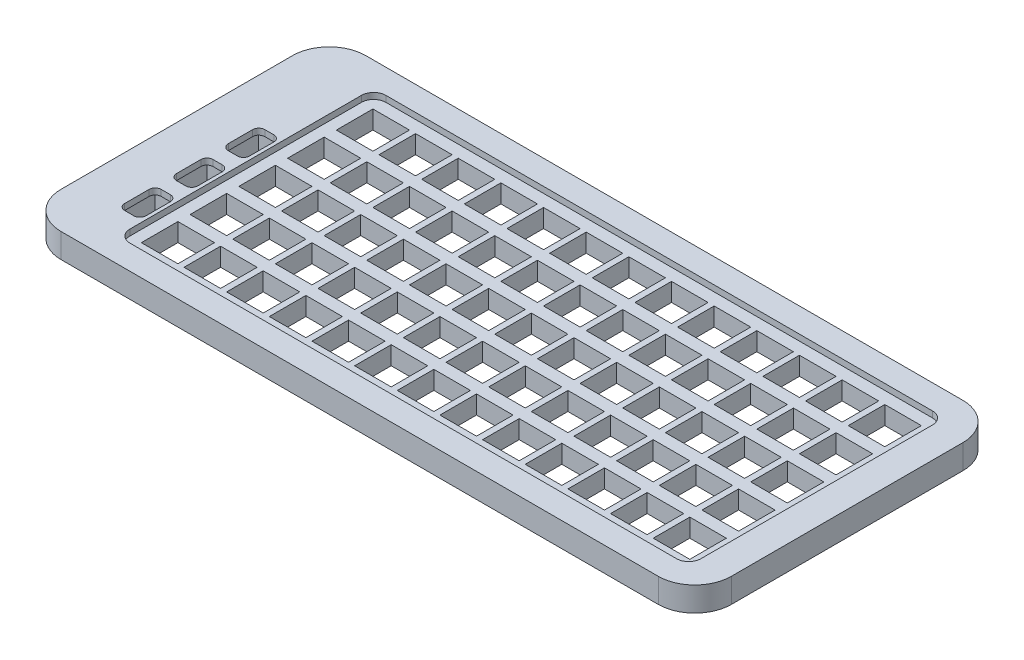
SolidWorks part; units mm, degrees
ref_plane "前视基准面" through (0, 0, 0) normal (0, 0, 1) x (1, 0, 0)
ref_plane "上视基准面" through (0, 0, 0) normal (0, 1, 0) x (1, 0, 0)
ref_plane "右视基准面" through (0, 0, 0) normal (1, 0, 0) x (0, 0, -1)
other "Configuration Table"
sketch "草图1" plane through (0, 0, 0) normal (0, 1, 0) x (1, 0, 0)
  line L1 (-55, -25) -> (55, -25)
  line L2 (-55, -25) -> (-55, 25)
  line L3 (-55, 25) -> (55, 25)
  line L4 (55, -25) -> (55, 25)
  line L5 (-55, -25) -> (55, 25) construction
  line L6 (-55, 25) -> (55, -25) construction
  point P0 (0, 0)
  dimension "D1" = 50
  dimension "D2" = 110
extrude "凸台-拉伸1" add sketch "草图1" along normal blind 3
sketch "草图2" plane through (0, 0, 0) normal (0, -1, 0) x (1, 0, 0)
  line L0 (46.3251, 14.2) -> (44.0251, 17.8) construction
  line L1 (48.1751, 11) -> (48.1751, 5)
  line L2 (48.1751, 19) -> (42.1751, 19)
  line L3 (48.1751, 19) -> (48.1751, 13)
  line L4 (48.1751, 13) -> (42.1751, 13)
  line L5 (42.1751, 19) -> (42.1751, 13)
  line L6 (48.1751, 19) -> (42.1751, 13) construction
  line L7 (48.1751, 13) -> (42.1751, 19) construction
  line L8 (48.1751, 5) -> (42.1751, 5)
  line L9 (42.1751, 11) -> (42.1751, 5)
  line L10 (48.1751, 11) -> (42.1751, 11)
  line L11 (48.1751, 3) -> (48.1751, -3)
  line L12 (48.1751, -3) -> (42.1751, -3)
  line L13 (42.1751, 3) -> (42.1751, -3)
  line L14 (48.1751, 3) -> (42.1751, 3)
  line L15 (48.1751, -5) -> (48.1751, -11)
  line L16 (48.1751, -11) -> (42.1751, -11)
  line L17 (42.1751, -5) -> (42.1751, -11)
  line L18 (48.1751, -5) -> (42.1751, -5)
  line L19 (48.1751, -13) -> (48.1751, -19)
  line L20 (48.1751, -19) -> (42.1751, -19)
  line L21 (42.1751, -13) -> (42.1751, -19)
  line L22 (48.1751, -13) -> (42.1751, -13)
  line L23 (41.1751, 11) -> (41.1751, 5)
  line L24 (41.1751, 5) -> (35.1751, 5)
  line L25 (35.1751, 11) -> (35.1751, 5)
  line L26 (41.1751, 11) -> (35.1751, 11)
  line L27 (41.1751, 3) -> (41.1751, -3)
  line L28 (41.1751, -3) -> (35.1751, -3)
  line L29 (35.1751, 3) -> (35.1751, -3)
  line L30 (41.1751, 3) -> (35.1751, 3)
  line L31 (41.1751, -5) -> (41.1751, -11)
  line L32 (41.1751, -11) -> (35.1751, -11)
  line L33 (35.1751, -5) -> (35.1751, -11)
  line L34 (41.1751, -5) -> (35.1751, -5)
  line L35 (41.1751, -13) -> (41.1751, -19)
  line L36 (41.1751, -19) -> (35.1751, -19)
  line L37 (35.1751, -13) -> (35.1751, -19)
  line L38 (41.1751, -13) -> (35.1751, -13)
  line L39 (34.1751, 11) -> (34.1751, 5)
  line L40 (34.1751, 5) -> (28.1751, 5)
  line L41 (28.1751, 11) -> (28.1751, 5)
  line L42 (34.1751, 11) -> (28.1751, 11)
  line L43 (34.1751, 3) -> (34.1751, -3)
  line L44 (34.1751, -3) -> (28.1751, -3)
  line L45 (28.1751, 3) -> (28.1751, -3)
  line L46 (34.1751, 3) -> (28.1751, 3)
  line L47 (34.1751, -5) -> (34.1751, -11)
  line L48 (34.1751, -11) -> (28.1751, -11)
  line L49 (28.1751, -5) -> (28.1751, -11)
  line L50 (34.1751, -5) -> (28.1751, -5)
  line L51 (34.1751, -13) -> (34.1751, -19)
  line L52 (34.1751, -19) -> (28.1751, -19)
  line L53 (28.1751, -13) -> (28.1751, -19)
  line L54 (34.1751, -13) -> (28.1751, -13)
  line L55 (27.1751, 11) -> (27.1751, 5)
  line L56 (27.1751, 5) -> (21.1751, 5)
  line L57 (21.1751, 11) -> (21.1751, 5)
  line L58 (27.1751, 11) -> (21.1751, 11)
  line L59 (27.1751, 3) -> (27.1751, -3)
  line L60 (27.1751, -3) -> (21.1751, -3)
  line L61 (21.1751, 3) -> (21.1751, -3)
  line L62 (27.1751, 3) -> (21.1751, 3)
  line L63 (27.1751, -5) -> (27.1751, -11)
  line L64 (27.1751, -11) -> (21.1751, -11)
  line L65 (21.1751, -5) -> (21.1751, -11)
  line L66 (27.1751, -5) -> (21.1751, -5)
  line L67 (27.1751, -13) -> (27.1751, -19)
  line L68 (27.1751, -19) -> (21.1751, -19)
  line L69 (21.1751, -13) -> (21.1751, -19)
  line L70 (27.1751, -13) -> (21.1751, -13)
  line L71 (20.1751, 11) -> (20.1751, 5)
  line L72 (20.1751, 5) -> (14.1751, 5)
  line L73 (14.1751, 11) -> (14.1751, 5)
  line L74 (20.1751, 11) -> (14.1751, 11)
  line L75 (20.1751, 3) -> (20.1751, -3)
  line L76 (20.1751, -3) -> (14.1751, -3)
  line L77 (14.1751, 3) -> (14.1751, -3)
  line L78 (20.1751, 3) -> (14.1751, 3)
  line L79 (20.1751, -5) -> (20.1751, -11)
  line L80 (20.1751, -11) -> (14.1751, -11)
  line L81 (14.1751, -5) -> (14.1751, -11)
  line L82 (20.1751, -5) -> (14.1751, -5)
  line L83 (20.1751, -13) -> (20.1751, -19)
  line L84 (20.1751, -19) -> (14.1751, -19)
  line L85 (14.1751, -13) -> (14.1751, -19)
  line L86 (20.1751, -13) -> (14.1751, -13)
  line L87 (13.1751, 11) -> (13.1751, 5)
  line L88 (13.1751, 5) -> (7.1751, 5)
  line L89 (7.1751, 11) -> (7.1751, 5)
  line L90 (13.1751, 11) -> (7.1751, 11)
  line L91 (13.1751, 3) -> (13.1751, -3)
  line L92 (13.1751, -3) -> (7.1751, -3)
  line L93 (7.1751, 3) -> (7.1751, -3)
  line L94 (13.1751, 3) -> (7.1751, 3)
  line L95 (13.1751, -5) -> (13.1751, -11)
  line L96 (13.1751, -11) -> (7.1751, -11)
  line L97 (7.1751, -5) -> (7.1751, -11)
  line L98 (13.1751, -5) -> (7.1751, -5)
  line L99 (13.1751, -13) -> (13.1751, -19)
  line L100 (13.1751, -19) -> (7.1751, -19)
  line L101 (7.1751, -13) -> (7.1751, -19)
  line L102 (13.1751, -13) -> (7.1751, -13)
  line L103 (6.1751, 11) -> (6.1751, 5)
  line L104 (6.1751, 5) -> (0.1751, 5)
  line L105 (0.1751, 11) -> (0.1751, 5)
  line L106 (6.1751, 11) -> (0.1751, 11)
  line L107 (6.1751, 3) -> (6.1751, -3)
  line L108 (6.1751, -3) -> (0.1751, -3)
  line L109 (0.1751, 3) -> (0.1751, -3)
  line L110 (6.1751, 3) -> (0.1751, 3)
  line L111 (6.1751, -5) -> (6.1751, -11)
  line L112 (6.1751, -11) -> (0.1751, -11)
  line L113 (0.1751, -5) -> (0.1751, -11)
  line L114 (6.1751, -5) -> (0.1751, -5)
  line L115 (6.1751, -13) -> (6.1751, -19)
  line L116 (6.1751, -19) -> (0.1751, -19)
  line L117 (0.1751, -13) -> (0.1751, -19)
  line L118 (6.1751, -13) -> (0.1751, -13)
  line L119 (-0.8249, 11) -> (-0.8249, 5)
  line L120 (-0.8249, 5) -> (-6.8249, 5)
  line L121 (-6.8249, 11) -> (-6.8249, 5)
  line L122 (-0.8249, 11) -> (-6.8249, 11)
  line L123 (-0.8249, 3) -> (-0.8249, -3)
  line L124 (-0.8249, -3) -> (-6.8249, -3)
  line L125 (-6.8249, 3) -> (-6.8249, -3)
  line L126 (-0.8249, 3) -> (-6.8249, 3)
  line L127 (-0.8249, -5) -> (-0.8249, -11)
  line L128 (-0.8249, -11) -> (-6.8249, -11)
  line L129 (-6.8249, -5) -> (-6.8249, -11)
  line L130 (-0.8249, -5) -> (-6.8249, -5)
  line L131 (-0.8249, -13) -> (-0.8249, -19)
  line L132 (-0.8249, -19) -> (-6.8249, -19)
  line L133 (-6.8249, -13) -> (-6.8249, -19)
  line L134 (-0.8249, -13) -> (-6.8249, -13)
  line L135 (-7.8249, 11) -> (-7.8249, 5)
  line L136 (-7.8249, 5) -> (-13.8249, 5)
  line L137 (-13.8249, 11) -> (-13.8249, 5)
  line L138 (-7.8249, 11) -> (-13.8249, 11)
  line L139 (-7.8249, 3) -> (-7.8249, -3)
  line L140 (-7.8249, -3) -> (-13.8249, -3)
  line L141 (-13.8249, 3) -> (-13.8249, -3)
  line L142 (-7.8249, 3) -> (-13.8249, 3)
  line L143 (-7.8249, -5) -> (-7.8249, -11)
  line L144 (-7.8249, -11) -> (-13.8249, -11)
  line L145 (-13.8249, -5) -> (-13.8249, -11)
  line L146 (-7.8249, -5) -> (-13.8249, -5)
  line L147 (-7.8249, -13) -> (-7.8249, -19)
  line L148 (-7.8249, -19) -> (-13.8249, -19)
  line L149 (-13.8249, -13) -> (-13.8249, -19)
  line L150 (-7.8249, -13) -> (-13.8249, -13)
  line L151 (-14.8249, 11) -> (-14.8249, 5)
  line L152 (-14.8249, 5) -> (-20.8249, 5)
  line L153 (-20.8249, 11) -> (-20.8249, 5)
  line L154 (-14.8249, 11) -> (-20.8249, 11)
  line L155 (-14.8249, 3) -> (-14.8249, -3)
  line L156 (-14.8249, -3) -> (-20.8249, -3)
  line L157 (-20.8249, 3) -> (-20.8249, -3)
  line L158 (-14.8249, 3) -> (-20.8249, 3)
  line L159 (-14.8249, -5) -> (-14.8249, -11)
  line L160 (-14.8249, -11) -> (-20.8249, -11)
  line L161 (-20.8249, -5) -> (-20.8249, -11)
  line L162 (-14.8249, -5) -> (-20.8249, -5)
  line L163 (-14.8249, -13) -> (-14.8249, -19)
  line L164 (-14.8249, -19) -> (-20.8249, -19)
  line L165 (-20.8249, -13) -> (-20.8249, -19)
  line L166 (-14.8249, -13) -> (-20.8249, -13)
  line L167 (-21.8249, 11) -> (-21.8249, 5)
  line L168 (-21.8249, 5) -> (-27.8249, 5)
  line L169 (-27.8249, 11) -> (-27.8249, 5)
  line L170 (-21.8249, 11) -> (-27.8249, 11)
  line L171 (-21.8249, 3) -> (-21.8249, -3)
  line L172 (-21.8249, -3) -> (-27.8249, -3)
  line L173 (-27.8249, 3) -> (-27.8249, -3)
  line L174 (-21.8249, 3) -> (-27.8249, 3)
  line L175 (-21.8249, -5) -> (-21.8249, -11)
  line L176 (-21.8249, -11) -> (-27.8249, -11)
  line L177 (-27.8249, -5) -> (-27.8249, -11)
  line L178 (-21.8249, -5) -> (-27.8249, -5)
  line L179 (-21.8249, -13) -> (-21.8249, -19)
  line L180 (-21.8249, -19) -> (-27.8249, -19)
  line L181 (-27.8249, -13) -> (-27.8249, -19)
  line L182 (-21.8249, -13) -> (-27.8249, -13)
  line L183 (-28.8249, 11) -> (-28.8249, 5)
  line L184 (-28.8249, 5) -> (-34.8249, 5)
  line L185 (-34.8249, 11) -> (-34.8249, 5)
  line L186 (-28.8249, 11) -> (-34.8249, 11)
  line L187 (-28.8249, 3) -> (-28.8249, -3)
  line L188 (-28.8249, -3) -> (-34.8249, -3)
  line L189 (-34.8249, 3) -> (-34.8249, -3)
  line L190 (-28.8249, 3) -> (-34.8249, 3)
  line L191 (-28.8249, -5) -> (-28.8249, -11)
  line L192 (-28.8249, -11) -> (-34.8249, -11)
  line L193 (-34.8249, -5) -> (-34.8249, -11)
  line L194 (-28.8249, -5) -> (-34.8249, -5)
  line L195 (-28.8249, -13) -> (-28.8249, -19)
  line L196 (-28.8249, -19) -> (-34.8249, -19)
  line L197 (-34.8249, -13) -> (-34.8249, -19)
  line L198 (-28.8249, -13) -> (-34.8249, -13)
  line L199 (-35.8249, 11) -> (-35.8249, 5)
  line L200 (-35.8249, 5) -> (-41.8249, 5)
  line L201 (-41.8249, 11) -> (-41.8249, 5)
  line L202 (-35.8249, 11) -> (-41.8249, 11)
  line L203 (-35.8249, 3) -> (-35.8249, -3)
  line L204 (-35.8249, -3) -> (-41.8249, -3)
  line L205 (-41.8249, 3) -> (-41.8249, -3)
  line L206 (-35.8249, 3) -> (-41.8249, 3)
  line L207 (-35.8249, -5) -> (-35.8249, -11)
  line L208 (-35.8249, -11) -> (-41.8249, -11)
  line L209 (-41.8249, -5) -> (-41.8249, -11)
  line L210 (-35.8249, -5) -> (-41.8249, -5)
  line L211 (-35.8249, -13) -> (-35.8249, -19)
  line L212 (-35.8249, -19) -> (-41.8249, -19)
  line L213 (-41.8249, -13) -> (-41.8249, -19)
  line L214 (-35.8249, -13) -> (-41.8249, -13)
  line L215 (41.1751, 19) -> (41.1751, 13)
  line L216 (41.1751, 13) -> (35.1751, 13)
  line L217 (35.1751, 19) -> (35.1751, 13)
  line L218 (41.1751, 19) -> (35.1751, 19)
  line L219 (34.1751, 19) -> (34.1751, 13)
  line L220 (34.1751, 13) -> (28.1751, 13)
  line L221 (28.1751, 19) -> (28.1751, 13)
  line L222 (34.1751, 19) -> (28.1751, 19)
  line L223 (27.1751, 19) -> (27.1751, 13)
  line L224 (27.1751, 13) -> (21.1751, 13)
  line L225 (21.1751, 19) -> (21.1751, 13)
  line L226 (27.1751, 19) -> (21.1751, 19)
  line L227 (20.1751, 19) -> (20.1751, 13)
  line L228 (20.1751, 13) -> (14.1751, 13)
  line L229 (14.1751, 19) -> (14.1751, 13)
  line L230 (20.1751, 19) -> (14.1751, 19)
  line L231 (13.1751, 19) -> (13.1751, 13)
  line L232 (13.1751, 13) -> (7.1751, 13)
  line L233 (7.1751, 19) -> (7.1751, 13)
  line L234 (13.1751, 19) -> (7.1751, 19)
  line L235 (6.1751, 19) -> (6.1751, 13)
  line L236 (6.1751, 13) -> (0.1751, 13)
  line L237 (0.1751, 19) -> (0.1751, 13)
  line L238 (6.1751, 19) -> (0.1751, 19)
  line L239 (-0.8249, 19) -> (-0.8249, 13)
  line L240 (-0.8249, 13) -> (-6.8249, 13)
  line L241 (-6.8249, 19) -> (-6.8249, 13)
  line L242 (-0.8249, 19) -> (-6.8249, 19)
  line L243 (-7.8249, 19) -> (-7.8249, 13)
  line L244 (-7.8249, 13) -> (-13.8249, 13)
  line L245 (-13.8249, 19) -> (-13.8249, 13)
  line L246 (-7.8249, 19) -> (-13.8249, 19)
  line L247 (-14.8249, 19) -> (-14.8249, 13)
  line L248 (-14.8249, 13) -> (-20.8249, 13)
  line L249 (-20.8249, 19) -> (-20.8249, 13)
  line L250 (-14.8249, 19) -> (-20.8249, 19)
  line L251 (-21.8249, 19) -> (-21.8249, 13)
  line L252 (-21.8249, 13) -> (-27.8249, 13)
  line L253 (-27.8249, 19) -> (-27.8249, 13)
  line L254 (-21.8249, 19) -> (-27.8249, 19)
  line L255 (-28.8249, 19) -> (-28.8249, 13)
  line L256 (-28.8249, 13) -> (-34.8249, 13)
  line L257 (-34.8249, 19) -> (-34.8249, 13)
  line L258 (-28.8249, 19) -> (-34.8249, 19)
  line L259 (-35.8249, 19) -> (-35.8249, 13)
  line L260 (-35.8249, 13) -> (-41.8249, 13)
  line L261 (-41.8249, 19) -> (-41.8249, 13)
  line L262 (-35.8249, 19) -> (-41.8249, 19)
  point P2 (45.1751, 16)
  dimension "D1" = 6
  dimension "D2" = 6
  dimension "D3" = 5
  dimension "D4" = 13
extrude "切除-拉伸1" cut sketch "草图2" against normal blind 10
sketch "草图3" plane through (0, 3, 0) normal (0, 1, 0) x (1, 0, 0)
  line L0 (-55, 25) -> (-55, -25) construction
  line L1 (-55, 25) -> (55, 25)
  line L2 (-55, 25) -> (-55, -25)
  line L3 (-55, -25) -> (55, -25)
  line L4 (55, 25) -> (55, -25)
  line L5 (55, 25) -> (-55, 25) construction
  line L6 (55, -25) -> (55, 25) construction
  line L7 (-55, -25) -> (55, -25) construction
  line L9 (-43.7, 21) -> (50, 21)
  line L10 (-43.7, 21) -> (-43.7, -21)
  line L11 (-43.7, -21) -> (50, -21)
  line L12 (50, 21) -> (50, -21)
  dimension "D1" = 4
  dimension "D2" = 4
  dimension "D3" = 5
  dimension "D4" = 42
  dimension "D5" = 11.3
extrude "凸台-拉伸2" add sketch "草图3" along normal blind 1
fillet "圆角1" radius 6 4 edges at (-55, 2, -25) (-55, 2, 25) (55, 2, 25) (55, 2, -25)
sketch "草图4" plane through (0, 0, 0) normal (0, -1, 0) x (1, 0, 0)
  line L0 (-45.3973, -4.764) -> (-46.6251, -1.636) construction
  line L1 (-45.3973, 3.736) -> (-46.6251, 6.864) construction
  line L2 (-45.2612, -0.2) -> (-46.7612, -0.2)
  line L3 (-44.2612, -1.2) -> (-44.2612, -5.2)
  line L4 (-45.2612, -6.2) -> (-46.7612, -6.2)
  line L5 (-47.7612, -1.2) -> (-47.7612, -5.2)
  line L6 (-44.2612, -0.2) -> (-47.7612, -6.2) construction
  line L7 (-44.2612, -6.2) -> (-47.7612, -0.2) construction
  line L8 (-44.2612, 7.3) -> (-44.2612, 3.3)
  line L9 (-45.2612, 8.3) -> (-46.7612, 8.3)
  line L10 (-47.7612, 7.3) -> (-47.7612, 3.3)
  line L11 (-45.2612, 2.3) -> (-46.7612, 2.3)
  line L12 (-45.3973, 12.236) -> (-46.6251, 15.364) construction
  line L13 (-44.2612, 15.8) -> (-44.2612, 11.8)
  line L14 (-45.2612, 16.8) -> (-46.7612, 16.8)
  line L15 (-47.7612, 15.8) -> (-47.7612, 11.8)
  line L16 (-45.2612, 10.8) -> (-46.7612, 10.8)
  arc A0 (-46.7612, 16.8) -> (-47.7612, 15.8) centre (-46.7612, 15.8) ccw
  arc A1 (-44.2612, 11.8) -> (-45.2612, 10.8) centre (-45.2612, 11.8) cw
  arc A2 (-44.2612, 15.8) -> (-45.2612, 16.8) centre (-45.2612, 15.8) ccw
  arc A3 (-47.7612, 11.8) -> (-46.7612, 10.8) centre (-46.7612, 11.8) ccw
  arc A4 (-46.7612, 8.3) -> (-47.7612, 7.3) centre (-46.7612, 7.3) ccw
  arc A5 (-44.2612, 3.3) -> (-45.2612, 2.3) centre (-45.2612, 3.3) cw
  arc A6 (-44.2612, 7.3) -> (-45.2612, 8.3) centre (-45.2612, 7.3) ccw
  arc A7 (-47.7612, 3.3) -> (-46.7612, 2.3) centre (-46.7612, 3.3) ccw
  arc A8 (-46.7612, -0.2) -> (-47.7612, -1.2) centre (-46.7612, -1.2) ccw
  arc A9 (-44.2612, -5.2) -> (-45.2612, -6.2) centre (-45.2612, -5.2) cw
  arc A10 (-45.2612, -0.2) -> (-44.2612, -1.2) centre (-45.2612, -1.2) cw
  arc A11 (-46.7612, -6.2) -> (-47.7612, -5.2) centre (-46.7612, -5.2) cw
  point P2 (-46.0112, -3.2)
  dimension "D4" = 1
  dimension "D1" = 3.5
  dimension "D2" = 6
  dimension "D3" = 3
extrude "切除-拉伸2" cut sketch "草图4" against normal blind 6
sketch "草图5" plane through (0, 0, 0) normal (0, -1, 0) x (1, 0, 0)
  line L0 (-46.0112, -6.2) -> (-46.0112, -0.2) construction
  line L1 (-46.7612, -6.2) -> (-45.2612, -6.2) construction
  line L2 (-45.2612, -0.2) -> (-46.7612, -0.2) construction
  line L3 (-43.7612, 8.8) -> (-43.7612, 1.8)
  line L4 (-43.7612, 0.3) -> (-48.2612, 0.3)
  line L5 (-43.7612, 0.3) -> (-43.7612, -6.7)
  line L6 (-43.7612, -6.7) -> (-48.2612, -6.7)
  line L7 (-48.2612, 0.3) -> (-48.2612, -6.7)
  line L8 (-43.7612, 0.3) -> (-48.2612, -6.7) construction
  line L9 (-43.7612, -6.7) -> (-48.2612, 0.3) construction
  line L10 (-43.7612, 8.8) -> (-48.2612, 8.8)
  line L11 (-48.2612, 8.8) -> (-48.2612, 1.8)
  line L12 (-43.7612, 1.8) -> (-48.2612, 1.8)
  line L13 (-43.7612, 17.3) -> (-43.7612, 10.3)
  line L14 (-43.7612, 17.3) -> (-48.2612, 17.3)
  line L15 (-48.2612, 17.3) -> (-48.2612, 10.3)
  line L16 (-43.7612, 10.3) -> (-48.2612, 10.3)
  point P6 (-46.0112, -3.2)
  dimension "D1" = 7
  dimension "D2" = 4.5
  dimension "D3" = 3
extrude "切除-拉伸3" cut sketch "草图5" against normal blind 3
fillet "圆角2" radius 2 4 edges at (50, 3.5, 21) (50, 3.5, -21) (-43.7, 3.5, -21) (-43.7, 3.5, 21)
